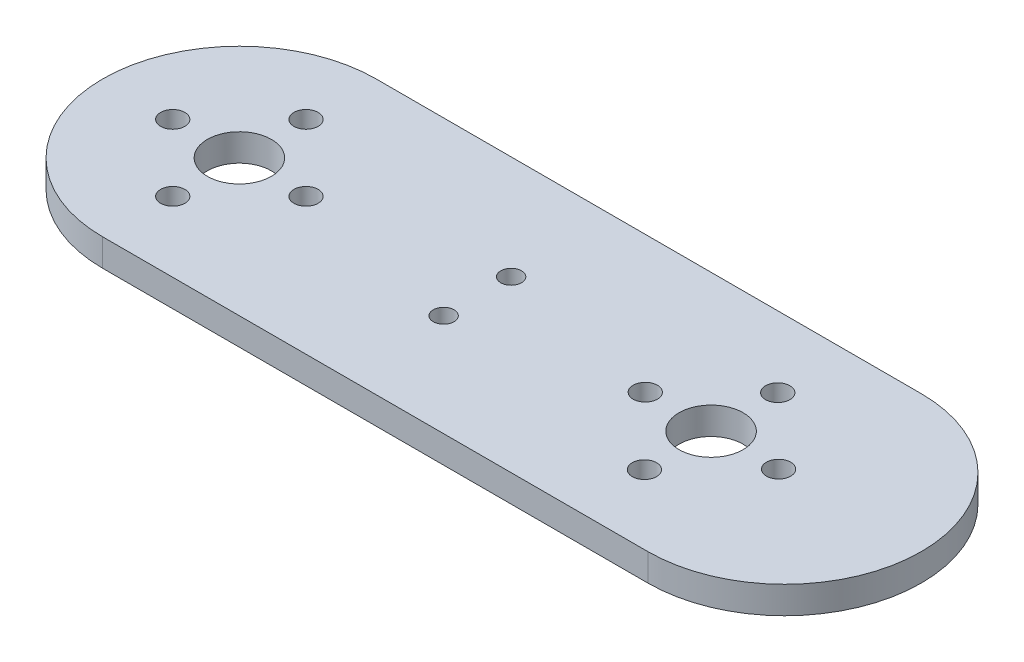
SolidWorks part; units mm, degrees
ref_plane "Front Plane" through (0, 0, 0) normal (0, 0, 1) x (1, 0, 0)
ref_plane "Top Plane" through (0, 0, 0) normal (0, 1, 0) x (1, 0, 0)
ref_plane "Right Plane" through (0, 0, 0) normal (1, 0, 0) x (0, 0, -1)
sketch "Sketch1" plane through (0, 0, 0) normal (0, 1, 0) x (1, 0, 0)
  line L0 (0, 15.5) -> (0, -15.5) construction
  line L1 (-15.5, 0) -> (15.5, 0) construction
  line L2 (-2.4674, 13.4022) -> (-4, 4) construction
  line L3 (4, -4) -> (-4, -4) construction
  line L4 (4, -4) -> (4, 4) construction
  line L5 (4, 4) -> (-4, 4) construction
  line L6 (-4, -4) -> (-4, 4) construction
  line L7 (4, -4) -> (-4, 4) construction
  line L8 (4, 4) -> (-4, -4) construction
  line L9 (-4, 4) -> (-2.4674, 13.4022)
  line L10 (4, 4) -> (2.4674, 13.4022)
  line L11 (4, -4) -> (2.4674, -13.4022)
  line L12 (-4, -4) -> (-2.4674, -13.4022)
  line L13 (-4, 4) -> (-12.5927, 2.4331) construction
  line L14 (-4, 4) -> (-12.4485, 2.4594)
  line L15 (-4, -4) -> (-12.4485, -2.4594)
  line L16 (4, -4) -> (12.4485, -2.4594)
  line L17 (4, 4) -> (12.4485, 2.4594)
  circle A0 centre (0, 0) radius 15.5 construction
  circle A1 centre (0, 0) radius 14.5 construction
  arc A2 (2.4674, 13.4022) -> (-2.4674, 13.4022) centre (0, 13) ccw
  arc A3 (2.4674, -13.4022) -> (-2.4674, -13.4022) centre (0, -13) cw
  arc A4 (-12.4485, 2.4594) -> (-12.4485, -2.4594) centre (-12, 0) ccw
  arc A5 (12.4485, 2.4594) -> (12.4485, -2.4594) centre (12, 0) cw
  circle A6 centre (0, 0) radius 12 construction
  circle A7 centre (0, 0) radius 9.5 construction
  circle A8 centre (0, 0) radius 7.5 construction
  circle A9 centre (0, 12) radius 0.5
  circle A10 centre (0, 9.5) radius 0.5
  circle A11 centre (0, 7.5) radius 0.5
  circle A12 centre (12, 0) radius 0.5
  circle A13 centre (9.5, 0) radius 0.5
  circle A14 centre (7.5, 0) radius 0.5
  circle A15 centre (0, -12) radius 0.5
  circle A16 centre (0, -9.5) radius 0.5
  circle A17 centre (0, -7.5) radius 0.5
  circle A18 centre (-12, 0) radius 0.5
  circle A19 centre (-9.5, 0) radius 0.5
  circle A20 centre (-7.5, 0) radius 0.5
  circle A21 centre (0, 0) radius 1.375
  point P59 (0, 0)
  dimension "D1" = 31
  dimension "D2" = 1
  dimension "D3" = 5
  dimension "D4" = 5
  dimension "D5" = 8
  dimension "D6" = 8
  dimension "D7" = 15
  dimension "D9" = 24
  dimension "D11" = 1
  dimension "D12" = 1
  dimension "D13" = 4
  dimension "D8" = 19
  dimension "D10" = 1
  dimension "D14" = 2.75
extrude "Boss-Extrude1" add sketch "Sketch1" along normal blind 2
sketch "Sketch4" plane through (0, 0, 0) normal (0, -1, 0) x (1, 0, 0)
  circle A0 centre (0, 0) radius 4.627
  circle A1 centre (0, 0) radius 2.627
  dimension "D1" = 9.254
  dimension "D2" = 2
extrude "Boss-Extrude3" add sketch "Sketch4" along normal blind 2.5
sketch "Sketch5" plane through (0, -2.5, 0) normal (0, -1, 0) x (1, 0, 0)
  line L0 (0, 0) -> (0, 0.6245) construction
  line L1 (0, 3.1016) -> (-0.2828, 2.6117)
  line L2 (0, 3.1016) -> (0.2828, 2.6117)
  line L3 (0.9584, 2.9498) -> (0.5381, 2.5713)
  line L4 (0.9584, 2.9498) -> (1.076, 2.3965)
  line L5 (1.8231, 2.5092) -> (1.3063, 2.2792)
  line L6 (1.8231, 2.5092) -> (1.7639, 1.9467)
  line L7 (2.5092, 1.8231) -> (1.9467, 1.7639)
  line L8 (2.5092, 1.8231) -> (2.2792, 1.3063)
  line L9 (2.9498, 0.9584) -> (2.3965, 1.076)
  line L10 (2.9498, 0.9584) -> (2.5713, 0.5381)
  line L11 (3.1016, 0) -> (2.6117, 0.2828)
  line L12 (3.1016, 0) -> (2.6117, -0.2828)
  line L13 (2.9498, -0.9584) -> (2.5713, -0.5381)
  line L14 (2.9498, -0.9584) -> (2.3965, -1.076)
  line L15 (2.5092, -1.8231) -> (2.2792, -1.3063)
  line L16 (2.5092, -1.8231) -> (1.9467, -1.7639)
  line L17 (1.8231, -2.5092) -> (1.7639, -1.9467)
  line L18 (1.8231, -2.5092) -> (1.3063, -2.2792)
  line L19 (0.9584, -2.9498) -> (1.076, -2.3965)
  line L20 (0.9584, -2.9498) -> (0.5381, -2.5713)
  line L21 (0, -3.1016) -> (0.2828, -2.6117)
  line L22 (0, -3.1016) -> (-0.2828, -2.6117)
  line L23 (-0.9584, -2.9498) -> (-0.5381, -2.5713)
  line L24 (-0.9584, -2.9498) -> (-1.076, -2.3965)
  line L25 (-1.8231, -2.5092) -> (-1.3063, -2.2792)
  line L26 (-1.8231, -2.5092) -> (-1.7639, -1.9467)
  line L27 (-2.5092, -1.8231) -> (-1.9467, -1.7639)
  line L28 (-2.5092, -1.8231) -> (-2.2792, -1.3063)
  line L29 (-2.9498, -0.9584) -> (-2.3965, -1.076)
  line L30 (-2.9498, -0.9584) -> (-2.5713, -0.5381)
  line L31 (-3.1016, 0) -> (-2.6117, -0.2828)
  line L32 (-3.1016, 0) -> (-2.6117, 0.2828)
  line L33 (-2.9498, 0.9584) -> (-2.5713, 0.5381)
  line L34 (-2.9498, 0.9584) -> (-2.3965, 1.076)
  line L35 (-2.5092, 1.8231) -> (-2.2792, 1.3063)
  line L36 (-2.5092, 1.8231) -> (-1.9467, 1.7639)
  line L37 (-1.8231, 2.5092) -> (-1.7639, 1.9467)
  line L38 (-1.8231, 2.5092) -> (-1.3063, 2.2792)
  line L39 (-0.9584, 2.9498) -> (-1.076, 2.3965)
  line L40 (-0.9584, 2.9498) -> (-0.5381, 2.5713)
  circle A0 centre (0, 0) radius 2.627 construction
  arc A1 (-2.2792, 1.3063) -> (-2.3965, 1.076) centre (0, 0) ccw
  arc A2 (-1.7639, 1.9467) -> (-1.9467, 1.7639) centre (0, 0) ccw
  arc A3 (-1.076, 2.3965) -> (-1.3063, 2.2792) centre (0, 0) ccw
  arc A4 (-0.2828, 2.6117) -> (-0.5381, 2.5713) centre (0, 0) ccw
  arc A5 (0.5381, 2.5713) -> (0.2828, 2.6117) centre (0, 0) ccw
  arc A6 (1.3063, 2.2792) -> (1.076, 2.3965) centre (0, 0) ccw
  arc A7 (1.9467, 1.7639) -> (1.7639, 1.9467) centre (0, 0) ccw
  arc A8 (2.3965, 1.076) -> (2.2792, 1.3063) centre (0, 0) ccw
  arc A9 (2.6117, 0.2828) -> (2.5713, 0.5381) centre (0, 0) ccw
  arc A10 (2.5713, -0.5381) -> (2.6117, -0.2828) centre (0, 0) ccw
  arc A11 (2.2792, -1.3063) -> (2.3965, -1.076) centre (0, 0) ccw
  arc A12 (1.7639, -1.9467) -> (1.9467, -1.7639) centre (0, 0) ccw
  arc A13 (1.076, -2.3965) -> (1.3063, -2.2792) centre (0, 0) ccw
  arc A14 (0.2828, -2.6117) -> (0.5381, -2.5713) centre (0, 0) ccw
  arc A15 (-0.5381, -2.5713) -> (0, -2.627) centre (0, 0) ccw
  arc A16 (-1.3063, -2.2792) -> (-1.076, -2.3965) centre (0, 0) ccw
  arc A17 (-1.9467, -1.7639) -> (-1.7639, -1.9467) centre (0, 0) ccw
  arc A18 (-2.3965, -1.076) -> (-2.2792, -1.3063) centre (0, 0) ccw
  arc A19 (-2.6117, -0.2828) -> (-2.5713, -0.5381) centre (0, 0) ccw
  arc A20 (-2.5713, 0.5381) -> (-2.6117, 0.2828) centre (0, 0) ccw
  point P68 (0, 0)
  circle M5 centre (0, 0) radius 2.627
  dimension "D1" = 30
  dimension "D2" = 3.1016
  dimension "D3" = 20
extrude "Cut-Extrude3" cut sketch "Sketch5" against normal up to surface (2.5 mm away) contours L36 L35 M5 | L34 L33 M5 | L32 L31 M5 | L30 L29 M5 | L28 L27 M5 | L26 L25 M5 | L24 L23 M5 | L0 L21 M5 | L22 L0 M5 | L20 L19 M5 | L18 L17 M5 | L16 L15 M5 | L14 L13 M5 | L12 L11 M5 | L10 L9 M5 | L8 L7 M5 | L6 L5 M5 | L4 L3 M5 | L0 L2 M5 | L0 L1 M5 | L40 L39 M5 | L38 L37 M5 region at (0, -2.5, 2.7818) region at (-0.8596, -2.5, 2.6457) region at (0.8596, -2.5, 2.6457) region at (-1.6351, -2.5, 2.2506) region at (1.6351, -2.5, 2.2506) region at (-2.2506, -2.5, 1.6351) region at (2.2506, -2.5, 1.6351) region at (-2.6457, -2.5, 0.8596) region at (2.6457, -2.5, 0.8596) region at (-2.7818, -2.5, 0) region at (2.7818, -2.5, 0) region at (-2.6457, -2.5, -0.8596) region at (2.6457, -2.5, -0.8596) region at (-2.2506, -2.5, -1.6351) region at (2.2506, -2.5, -1.6351) region at (-1.6351, -2.5, -2.2506) region at (1.6351, -2.5, -2.2506) region at (-0.8596, -2.5, -2.6457) region at (0.8596, -2.5, -2.6457) region at (0, -2.5, -2.7818) up to face at (0, 0, 1.375)
sketch "Sketch6" plane through (0, 2, 0) normal (0, 1, 0) x (1, 0, 0)
  circle A0 centre (0, 0) radius 20.066
  circle A2 centre (0, 0) radius 3.75
  dimension "D1" = 40.132
extrude "Boss-Extrude6" add sketch "Sketch6" against normal blind 2.54
sketch "Sketch7" plane through (0, 2, 0) normal (0, 1, 0) x (1, 0, 0)
  circle A0 centre (0, 9.779) radius 1.778
extrude "Cut-Extrude4" cut sketch "Sketch7" against normal blind 2.54
pattern_circular "CirPattern1" count 4 over 360 about axis through (0, 2, 0) along (0, -1, 0) of "Cut-Extrude4"
sketch "Esquisse1" plane through (0, 2, 0) normal (0, 1, 0) x (1, 0, 0)
  line L0 (0, 20.066) -> (80.01, 20.066)
  line L1 (0, -20.066) -> (80.01, -20.066)
  circle A0 centre (0, 0) radius 20.066 construction
  arc A1 (80.01, 20.066) -> (80.01, -20.066) centre (80.01, 0) cw
  arc A2 (0, -20.066) -> (0, 20.066) centre (0, 0) ccw
  dimension "D1" = 80.01
  dimension "D2" = 80.01
extrude "Boss.-Extru.1" add sketch "Esquisse1" along normal blind 2.2225 and the other way blind 2.54 contours L1 A1 L0 A2
sketch "Esquisse3" plane through (0, 2, 0) normal (0, 1, 0) x (1, 0, 0)
  circle A0 centre (0, 0) radius 20.066
  circle A1 centre (9.779, 0) radius 1.778
  circle A2 centre (0, 9.779) radius 1.778
  circle A3 centre (-9.779, 0) radius 1.778
  circle A4 centre (0, -9.779) radius 1.778
  circle A5 centre (0, 0) radius 1.375
extrude "Boss.-Extru.2" add sketch "Esquisse3" along normal blind 2.2225
sketch "Esquisse4" plane through (0, -0.54, 0) normal (0, -1, 0) x (1, 0, 0)
  line L0 (0, 20.066) -> (80.01, 20.066) construction
  line L1 (80.01, 10.16) -> (39.116, 10.16)
  line L2 (39.116, 10.16) -> (39.116, -9.906)
  line L3 (39.116, -9.906) -> (80.01, -9.906)
  line L4 (80.01, -9.906) -> (80.01, 10.16)
  dimension "D1" = 9.906
  dimension "D2" = 20.066
  dimension "D3" = 40.894
extrude "Enlèv. mat.-Extru.1" cut sketch "Esquisse4" against normal up to next
sketch "Esquisse5" plane through (0, -0.54, 0) normal (0, -1, 0) x (-1, 0, 0)
  line L0 (-39.116, -10.16) -> (-39.116, 9.906) construction
  line L1 (-39.116, 9.906) -> (-80.01, 9.906) construction
  line L2 (-80.01, -10.16) -> (-39.116, -10.16) construction
  line L3 (-80.01, 9.906) -> (-80.01, -10.16) construction
  circle A0 centre (-35.052, -5.08) radius 1.524
  circle A1 centre (-35.052, 4.826) radius 1.524
  circle A2 centre (-84.074, -5.08) radius 1.524
  circle A3 centre (-84.074, 4.826) radius 1.524
  dimension "D2" = 4.064
  dimension "D3" = 5.08
  dimension "D4" = 5.08
  dimension "D5" = 5.08
  dimension "D6" = 5.08
  dimension "D7" = 4.064
  dimension "D8" = 4.064
  dimension "D9" = 3.048
  dimension "D10" = 3.048
  dimension "D11" = 3.048
  dimension "D12" = 3.048
  dimension "D1" = 4.064
extrude "Enlèv. mat.-Extru.2" cut sketch "Esquisse5" against normal through all
sketch "Esquisse6" plane through (0, 4.2225, 0) normal (0, 1, 0) x (1, 0, 0)
  line L1 (-24.0414, -40.1247) -> (105.7665, -40.1247)
  line L2 (-24.0414, -40.1247) -> (-24.0414, 44.3818)
  line L3 (-24.0414, 44.3818) -> (105.7665, 44.3818)
  line L4 (105.7665, -40.1247) -> (105.7665, 44.3818)
extrude "Enlèv. mat.-Extru.3" cut sketch "Esquisse6" against normal blind 0.76
sketch "Esquisse7" plane through (0, -2.5, 0) normal (0, -1, 0) x (-1, 0, 0)
  circle A0 centre (0, 0) radius 4.7
  dimension "D1" = 9.4
extrude "Enlèv. mat.-Extru.4" cut sketch "Esquisse7" against normal through all
sketch "Esquisse8" plane through (0, -0.54, 0) normal (0, -1, 0) x (-1, 0, 0)
  line L1 (-39.116, 9.906) -> (-80.01, 9.906)
  line L2 (-39.116, 9.906) -> (-39.116, -10.16)
  line L3 (-39.116, -10.16) -> (-80.01, -10.16)
  line L4 (-80.01, 9.906) -> (-80.01, -10.16)
extrude "Boss.-Extru.3" add sketch "Esquisse8" against normal through all
sketch "Esquisse9" plane through (0, -0.54, 0) normal (0, -1, 0) x (-1, 0, 0)
  circle A0 centre (-69.344, -0.125) radius 4.7
  circle A1 centre (-84.074, -5.08) radius 1.524 construction
  dimension "D1" = 14.73
  dimension "D2" = 9.4
  dimension "D3" = 4.955
extrude "Enlèv. mat.-Extru.5" cut sketch "Esquisse9" against normal blind 10 contours A0
sketch "Esquisse11" plane through (0, 3.4625, 0) normal (0, 1, 0) x (1, 0, 0)
  circle A0 centre (69.344, 9.655) radius 1.78
  circle A2 centre (69.344, -9.905) radius 1.78
  circle A3 centre (59.564, 0) radius 1.78
  circle A5 centre (79.124, 0) radius 1.78
  circle A6 centre (69.344, -0.125) radius 4.7 construction
  dimension "D1" = 9.78
  dimension "D2" = 9.78
  dimension "D3" = 9.78
  dimension "D4" = 9.78
  dimension "D7" = 3.56
  dimension "D8" = 3.56
  dimension "D9" = 3.56
  dimension "D10" = 3.56
  dimension "D5" = 0
  dimension "D6" = 0
extrude "Enlèv. mat.-Extru.6" cut sketch "Esquisse11" against normal blind 10
sketch "Esquisse10" plane through (0, 3.4625, 0) normal (0, 1, 0) x (1, 0, 0)
  circle A4 centre (84.074, 4.826) radius 1.524
  circle A5 centre (84.074, -5.08) radius 1.524
extrude "Boss.-Extru.4" add sketch "Esquisse10" against normal through all
